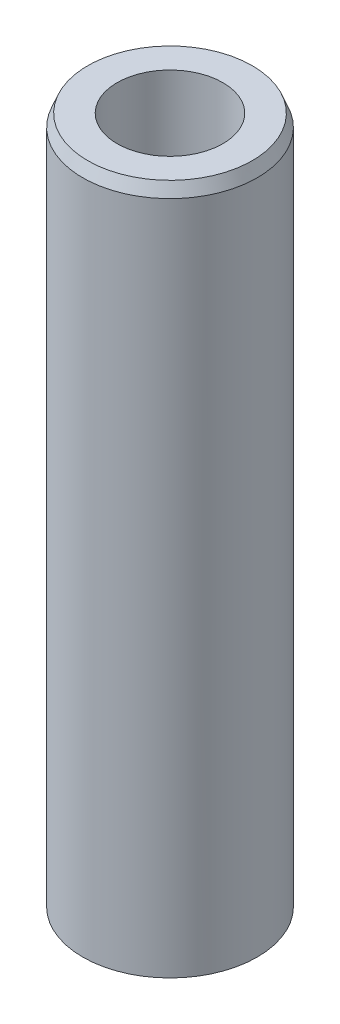
SolidWorks part; units mm, degrees
ref_plane "Front Plane" through (0, 0, 0) normal (0, 0, 1) x (1, 0, 0)
ref_plane "Top Plane" through (0, 0, 0) normal (0, 1, 0) x (1, 0, 0)
ref_plane "Right Plane" through (0, 0, 0) normal (1, 0, 0) x (0, 0, -1)
sketch "Sketch1" plane through (0, 0, 0) normal (0, 1, 0) x (1, 0, 0)
  circle A0 centre (0, 0) radius 7.5
  dimension "SHAFT_OD" = 15
extrude "Boss-Extrude1" add sketch "Sketch1" along normal blind 59.4866
sketch "Sketch2" plane through (0, 0, 0) normal (0, 1, 0) x (1, 0, 0)
  circle A0 centre (0, 0) radius 4.5467
  dimension "BORE_D" = 9.0933
extrude "Cut-Extrude1" cut sketch "Sketch2" along normal through all
chamfer "Chamfer1" distance 1.0606 angle 21.963 2 edges at (0, 59.4866, 7.5) (0, 0, 7.5) first distance on face at (0, 59.4866, 7.5) first distance on face at (0, 0, 4.5467)
